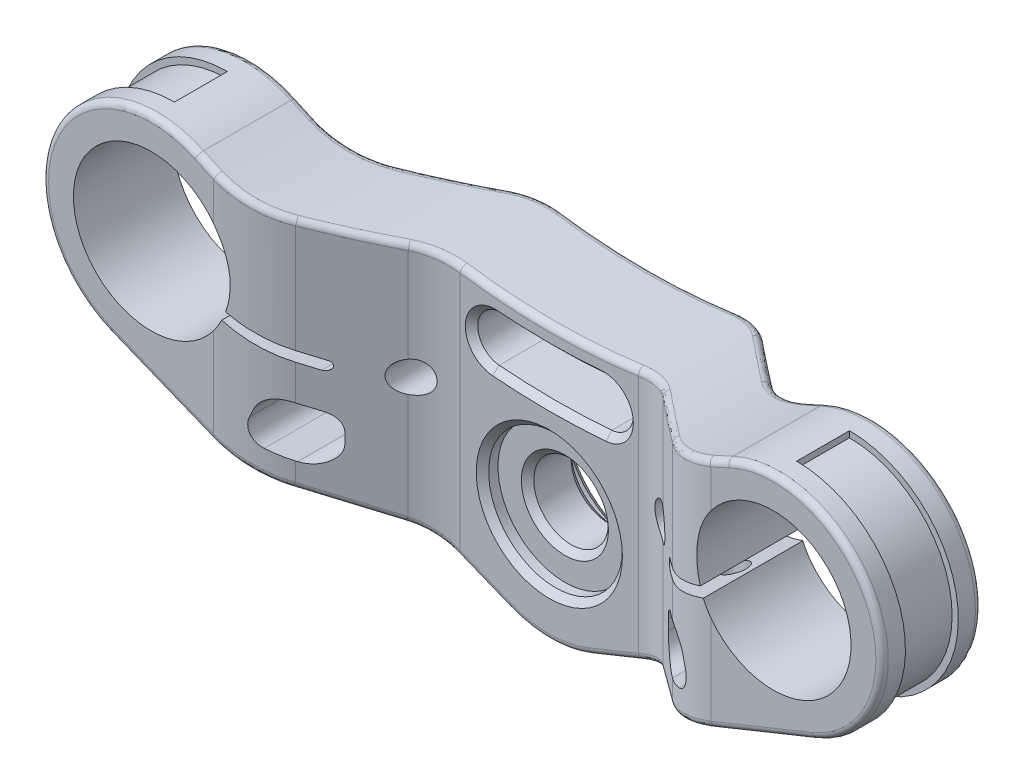
SolidWorks part; units mm, degrees
ref_plane "Front Plane" through (0, 0, 0) normal (0, 0, 1) x (1, 0, 0)
ref_plane "Top Plane" through (0, 0, 0) normal (0, 1, 0) x (1, 0, 0)
ref_plane "Right Plane" through (0, 0, 0) normal (1, 0, 0) x (0, 0, -1)
sketch "Sketch1" plane through (0, 0, 0) normal (0, 0, 1) x (1, 0, 0)
  line L0 (0, 218.4734) -> (0, -157.6301) construction
  line L1 (52, 3.6173) -> (52, 0.3817)
  line L2 (60.2476, -5.1814) -> (66.7379, -2.5592)
  line L3 (70.0534, 5.2516) -> (68.9296, 8.0331)
  line L4 (61.1188, 11.3486) -> (55.7524, 9.1804)
  line L5 (13.1112, -32.8541) -> (113.1112, 7.5486)
  line L6 (-13.1112, -32.8541) -> (-113.1112, 7.5486)
  line L11 (54.9333, 23.4097) -> (76.3003, 32.0425)
  line L12 (-54.9333, 23.4097) -> (-76.3003, 32.0425)
  line L13 (56.0571, 20.6281) -> (77.4241, 29.2609)
  line L14 (-56.0571, 20.6281) -> (-77.4241, 29.2609)
  line L15 (100, 40) -> (177.5237, 40) construction
  line L16 (55.4952, 22.0189) -> (100, 40) construction
  line L17 (-70.0534, 5.2516) -> (-68.9296, 8.0331)
  line L18 (-60.2476, -5.1814) -> (-66.7379, -2.5592)
  line L19 (-52, 3.6173) -> (-52, 0.3817)
  line L20 (-61.1188, 11.3486) -> (-55.7524, 9.1804)
  circle A0 centre (0, 0) radius 25
  circle A1 centre (40, 20) radius 5
  circle A2 centre (-40, 20) radius 5
  arc A3 (-17.5, 38.8768) -> (17.5, 38.8768) centre (0, 252.6617) ccw construction
  arc A4 (-18.1119, 31.4018) -> (18.1119, 31.4018) centre (0, 252.6617) ccw
  arc A5 (-16.8881, 46.3518) -> (16.8881, 46.3518) centre (0, 252.6617) ccw
  arc A6 (-16.8881, 46.3518) -> (-18.1119, 31.4018) centre (-17.5, 38.8768) ccw
  arc A7 (18.1119, 31.4018) -> (16.8881, 46.3518) centre (17.5, 38.8768) ccw
  circle A13 centre (100, 40) radius 35
  arc A14 (85.1064, 71.673) -> (-85.1064, 71.673) centre (0, 252.6617) cw
  circle A15 centre (-100, 40) radius 35
  circle A17 centre (100, 40) radius 25
  circle A18 centre (-100, 40) radius 25
  circle A19 centre (55.4952, 22.0189) radius 1.5
  circle A20 centre (-55.4952, 22.0189) radius 1.5
  arc A21 (13.1112, -32.8541) -> (-13.1112, -32.8541) centre (0, -0.4026) cw
  arc A22 (66.7379, -2.5592) -> (70.0534, 5.2516) centre (64.4903, 3.0039) ccw
  arc A23 (68.9296, 8.0331) -> (61.1188, 11.3486) centre (63.3665, 5.7855) ccw
  arc A24 (52, 3.6173) -> (55.7524, 9.1804) centre (58, 3.6173) cw
  arc A25 (52, 0.3817) -> (60.2476, -5.1814) centre (58, 0.3817) ccw
  arc A26 (-66.7379, -2.5592) -> (-70.0534, 5.2516) centre (-64.4903, 3.0039) cw
  arc A27 (-52, 0.3817) -> (-60.2476, -5.1814) centre (-58, 0.3817) cw
  arc A28 (-68.9296, 8.0331) -> (-61.1188, 11.3486) centre (-63.3665, 5.7855) cw
  arc A29 (-52, 3.6173) -> (-55.7524, 9.1804) centre (-58, 3.6173) ccw
  point P12 (0, 38.1617)
  point P35 (0, 0)
  point P49 (72.301, -0.3115)
  point P54 (0, -38.1513)
  point P59 (66.6819, 13.5962)
  point P62 (52, 7.6643)
  point P65 (52, -8.5137)
  dimension "D1" = 50
  dimension "D2" = 10
  dimension "D5" = 207
  dimension "D7" = 15
  dimension "D10" = 6
  dimension "D12" = 70
  dimension "D13" = 200
  dimension "D18" = 50
  dimension "D19" = 3
  dimension "D22" = 35
  dimension "D3" = 80
  dimension "D4" = 20
  dimension "D6" = 35
  dimension "D8" = 22
  dimension "D9" = 15
  dimension "D11" = 13
  dimension "D14" = 8
  dimension "D15" = 40
  dimension "D16" = 200
  dimension "D17" = 52
  dimension "D20" = 48
  dimension "D21" = 22
extrude "Boss-Extrude1" add sketch "Sketch1" along normal blind 60 contours A21 L5 A13 L13 A19 L11 A14 A15 L12 A20 L14 L6 A29 L19 A27 L18 A26 L17 A28 L20 A25 L1 A24 L4 A23 L3 A22 L2 A7 A4 A6 A5 A0 A1 A2 | A17 L13 A13 L11 | L14 A18 L12 A15 region at (0, -32.8998, 0) region at (87.3853, 8.416, 0) region at (-131.1674, 53.6116, 0)
sketch "Sketch3" plane through (0, 0, 0) normal (0, 1, 0) x (1, 0, 0)
  line L0 (0, 67.3745) -> (0, -122.9146) construction
  line L1 (60.6355, -52.9813) -> (40.9284, -36.4452)
  line L2 (135, -60) -> (79.9191, -60)
  line L3 (135, -60) -> (135, -28)
  line L4 (135, -28) -> (79.9191, -28)
  line L6 (-28.3515, 0) -> (28.3515, 0)
  line L7 (0, 0) -> (0, -32)
  line L8 (-28.7155, -32) -> (28.7155, -32)
  line L10 (60.6355, -20.9813) -> (41.2072, -4.6791)
  line L11 (13.1112, -60) -> (113.1112, -60) construction
  line L12 (-60.6355, -20.9813) -> (-41.2072, -4.6791)
  line L13 (-135, -28) -> (-79.9191, -28)
  line L14 (-135, -60) -> (-135, -28)
  line L15 (-135, -60) -> (-79.9191, -60)
  line L16 (-60.6355, -52.9813) -> (-40.9284, -36.4452)
  line L25 (174.0973, -109.1637) -> (-174.0973, -109.1637)
  line L26 (-174.0973, -109.1637) -> (-174.0973, 67.3745)
  line L27 (174.0973, -109.1637) -> (174.0973, 67.3745)
  line L28 (-174.0973, 67.3745) -> (174.0973, 67.3745)
  line L29 (135, -60) -> (174.0973, -60)
  line L30 (-135, -60) -> (-174.0973, -60)
  line L31 (135, -28) -> (174.0973, -28)
  line L32 (-135, -28) -> (-174.0973, -28)
  arc A0 (79.9191, -60) -> (60.6355, -52.9813) centre (79.9191, -30) cw
  arc A1 (60.6355, -20.9813) -> (79.9191, -28) centre (79.9191, 2) ccw
  arc A2 (-41.2072, -4.6791) -> (-28.3515, 0) centre (-28.3515, -20) cw
  arc A3 (28.3515, 0) -> (41.2072, -4.6791) centre (28.3515, -20) cw
  arc A4 (-40.9284, -36.4452) -> (-28.7155, -32) centre (-28.7155, -51) cw
  arc A5 (40.9284, -36.4452) -> (28.7155, -32) centre (28.7155, -51) ccw
  arc A6 (-79.9191, -60) -> (-60.6355, -52.9813) centre (-79.9191, -30) ccw
  arc A7 (-60.6355, -20.9813) -> (-79.9191, -28) centre (-79.9191, 2) cw
  point P22 (69, -60)
  point P25 (69, -28)
  point P28 (-35.6309, 0)
  point P31 (35.6309, 0)
  point P34 (-35.6309, -32)
  point P37 (35.6309, -32)
  point P40 (-69, -60)
  point P43 (-69, -28)
  point P47 (0, -109.1637)
  dimension "D6" = 30
  dimension "D7" = 20
  dimension "D8" = 19
  dimension "D9" = 30
  dimension "D1" = 32
  dimension "D2" = 66
  dimension "D3" = 32
  dimension "D4" = 35.6309
  dimension "D5" = 40
extrude "Cut-Extrude1" cut sketch "Sketch3" against normal through all both and the other way through all contours L28 L0 L6 A3 L10 A1 L4 L31 L27 | L0 L28 L26 L32 L13 A7 L12 A2 L6 | L14 L32 L26 L30 | L0 L8 A4 L16 A6 L15 L30 L26 L25 | L8 L0 L25 L27 L29 L2 A0 L1 A5 | L31 L3 L29 L27 region at (92.8523, 0, -23.1252) region at (-92.8523, 0, -23.1252) region at (78.2915, 0, 79.1586) region at (-78.2915, 0, 79.1586) region at (-154.5486, 0, 44) region at (154.5486, 0, 44)
hole_wizard "1/2 Rc Tapped Hole1" positions "3DSketch1" profile "Sketch6" size "1/2" standard "ISO"
sketch3d "3DSketch1"
  line L1 (79.9191, -5.8619, 60) -> (113.1112, 7.5486, 60) construction
  line L3 (84.085, -4.1788, 44) -> (49.0977, 65.166, 44)
  point P7 (84.085, -4.1788, 44)
  dimension "D1" = 16
sketch "Sketch6" plane through (84.085, -4.1788, 44) normal (0, 0, 1) x (0.9272, 0.3746, 0)
  line L0 (0, 0) -> (0, 59.4034)
  line L1 (4, 57) -> (0, 59.4034)
  line L2 (-4, 57) -> (0, 59.4034) construction
  line L3 (4, 57) -> (4, 10)
  line L4 (4, 10) -> (10.0093, 10)
  line L5 (10.0093, 10) -> (10.3214, 0)
  line L6 (-10.0093, 10) -> (-10.3214, 0) construction
  line L7 (10.3214, 0) -> (0, 0)
  line L8 (0, -6.35) -> (0, 107.95) construction
  line L11 (-4, 10) -> (-10.0093, 10) construction
  dimension "Tap Drill Dia." = 8
  dimension "Tap Drill Depth" = 57
  dimension "Thread Dia." = 20.6428
  dimension "Thread Angle" = 3.576
  dimension "Thread Depth" = 10
  dimension "Drill Angle" = 118
mirror "Mirror1" about plane through (0, 0, 0) normal (1, 0, 0) of "1/2 Rc Tapped Hole1"
sketch "Sketch7" plane through (0, 0, 0) normal (0, 0, -1) x (-1, 0, 0)
  circle A1 centre (0, 0) radius 25 construction
  circle A2 centre (0, 0) radius 12
  circle A3 centre (0, 0) radius 12
  circle A4 centre (0, 0) radius 25
  dimension "D1" = 13
extrude "Boss-Extrude6" add sketch "Sketch7" against normal offset from surface (16 mm away) 5 from offset 11 up to face at (0, 38.8252, 32) offset against normal yes
sketch "Sketch8" plane through (0, 0, 27) normal (0, 0, 1) x (1, 0, 0)
  circle A0 centre (0, 0) radius 25 construction
  circle A1 centre (0, 0) radius 25
  circle A2 centre (0, 0) radius 21.5
  dimension "D1" = 3.5
extrude "Boss-Extrude7" add sketch "Sketch8" along normal up to surface (5 mm away) up to face at (0, 38.8252, 32)
fillet "Fillet2" radius 2 44 edges at (35.0774, 55.7618, 33.0968) (50.848, 59.2335, 44.7686) (69.4999, 65.1257, 58.1325) (82.5211, 70.4797, 60) (132.0746, 54.0078, 60) (96.5152, 0.8433, 60) (69.6585, -10.0075, 58.1908) (50.782, -17.6341, 44.7132) (35.2138, -23.924, 33.1458) (20.9133, -29.7018, 32) (0, -35.4026, 32) (-20.9133, -29.7018, 32) (-35.2138, -23.924, 33.1458) (-50.782, -17.6341, 44.7132) (-69.6585, -10.0075, 58.1908) (-96.5152, 0.8433, 60) (-132.0746, 54.0078, 60) (-82.5211, 70.4797, 60) (-69.4999, 65.1257, 58.1325) (-50.848, 59.2335, 44.7686) (-35.0774, 55.7618, 33.0968) (35.3301, 55.807, 1.257) (50.9857, 59.2697, 12.8842) (69.6864, 65.1949, 26.2009) (82.5211, 70.4797, 28) (132.0746, 54.0078, 28) (96.5152, 0.8433, 28) (69.6585, -10.0075, 26.1908) (50.9214, -17.5778, 12.8302) (35.1919, -23.9329, 1.2061) (20.7314, -29.7753, 0) (0, -35.4026, 0) (-20.7314, -29.7753, 0) (-35.1919, -23.9329, 1.2061) (-50.9214, -17.5778, 12.8302) (-69.6585, -10.0075, 26.1908) (-96.5152, 0.8433, 28) (-132.0746, 54.0078, 28) (-82.5211, 70.4797, 28) (-69.6864, 65.1949, 26.2009) (-50.9857, 59.2697, 12.8842) (-35.0465, 55.7563, 1.1539) (0, 52.6617, 32) (0, 52.6617, 0)
ref_plane "Plane1" through (0, 0, 44) normal (0, 0, -1) x (-1, 0, 0)
sketch "Sketch9" plane through (0, 0, 44) normal (0, 0, -1) x (-1, 0, 0)
  line L0 (-100, 98.114) -> (-100, 73)
  line L1 (-100, 7) -> (-100, -18.114)
  arc A0 (-100, 73) -> (-100, 7) centre (-100, 40) ccw
  arc A1 (-100, 98.114) -> (-100, -18.114) centre (-100, 40) ccw
  dimension "D1" = 66
  dimension "D2" = 116.2281
extrude "Cut-Extrude2" cut sketch "Sketch9" against normal mid plane 17
mirror "Mirror2" about plane through (0, 0, 0) normal (1, 0, 0) of "Cut-Extrude2"
chamfer "Chamfer1" distance 2 angle 45 12 edges at (-12, 0, 11) (0, 30.6617, 32) (-24.975, 39.4887, 32) (24.975, 39.4887, 32) (0, 45.6617, 32) (21.5, 0, 32) (12, 0, 27) (0, 30.6617, 0) (-24.975, 39.4887, 0) (24.975, 39.4887, 0) (0, 45.6617, 0) (25, 0, 0)
fillet "Fillet3" radius 2 20 edges at (69.7183, 0.0597, 26.2125) (63.5659, -3.8408, 23.151) (60.4416, -5.1031, 20.8186) (54.6448, -4.5926, 15.9546) (52, 1.9995, 13.7353) (53.0258, 6.9724, 14.596) (58.1939, 10.1668, 18.9326) (60.8761, 11.2505, 21.1811) (66.4978, 10.9035, 24.8304) (-52, 1.9995, 13.7353) (-54.6448, -4.5926, 15.9546) (-60.4416, -5.1031, 20.8186) (-63.5659, -3.8408, 23.151) (-70.2934, 1.4796, 26.4138) (-69.4894, 6.6475, 26.1287) (-65.6582, 11.3305, 24.3937) (-60.8761, 11.2505, 21.1811) (-58.1939, 10.1668, 18.9326) (69.4894, 6.6475, 26.1287) (-53.0258, 6.9724, 14.596)
